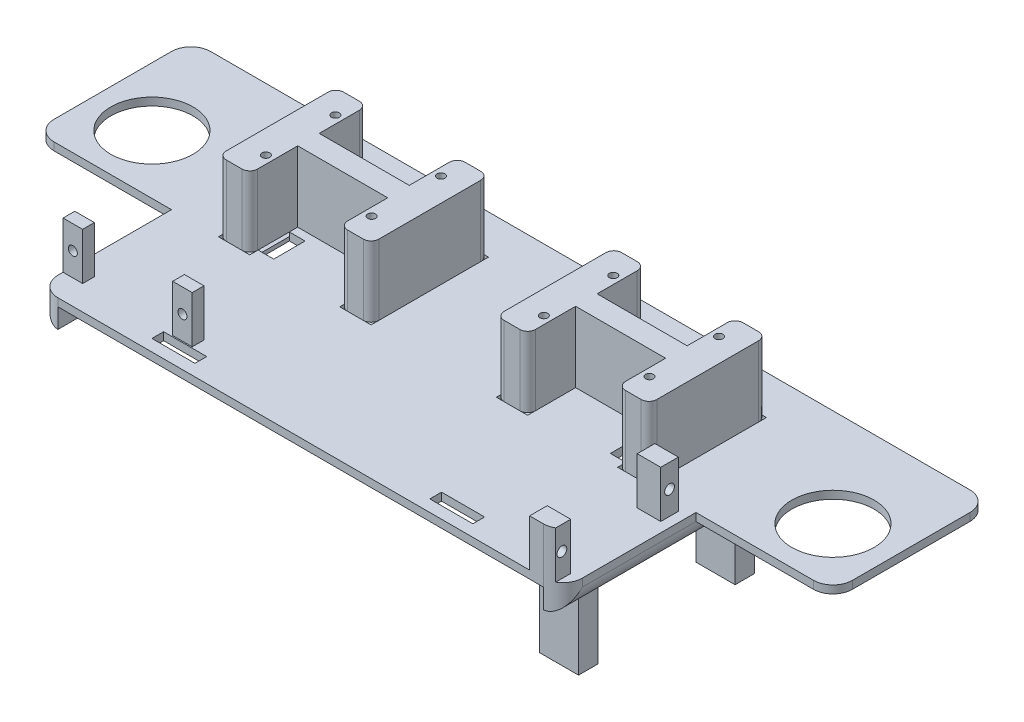
SolidWorks part; units mm, degrees
other "Controller Base"
other "HMount1"
other "HMount2"
ref_plane "Front Plane" through (0, 0, 0) normal (0, 0, 1) x (1, 0, 0)
ref_plane "Top Plane" through (0, 0, 0) normal (0, 1, 0) x (1, 0, 0)
ref_plane "Right Plane" through (0, 0, 0) normal (1, 0, 0) x (0, 0, -1)
sketch "Sketch1" plane through (0, 0, 0) normal (1, 0, 0) x (0, 0, -1)
  line L0 (0, 0) -> (0, 30)
  line L1 (0, 30) -> (45, 30)
  line L2 (45, 30) -> (45, 0)
  line L3 (45, 0) -> (40, 0)
  line L4 (40, 0) -> (40, 27)
  line L5 (40, 27) -> (5, 27)
  line L6 (5, 27) -> (5, 0)
  line L7 (5, 0) -> (0, 0)
  dimension "D1" = 5
  dimension "D2" = 5
  dimension "D3" = 3
  dimension "D4" = 35
  dimension "D5" = 30
extrude "C Bracket" add sketch "Sketch1" along normal blind 10
sketch "Sketch3" plane through (0, 30, 0) normal (0, 1, 0) x (1, 0, 0)
  line L0 (10, 45) -> (10, 0) construction
  line L1 (-113, -15) -> (21, -15)
  line L2 (-113, -15) -> (-113, 59)
  line L3 (-113, 59) -> (21, 59)
  line L4 (21, -15) -> (21, 59)
  line L5 (10, 0) -> (0, 0) construction
  line L6 (-148, 19) -> (-148, 59)
  line L7 (-113, 59) -> (-148, 59)
  line L8 (-46, 59) -> (-46, -15) construction
  line L9 (-113, 19) -> (-113, 59)
  line L10 (21, 19) -> (56, 19)
  line L11 (21, 19) -> (21, 59)
  line L12 (21, 59) -> (56, 59)
  line L13 (56, 19) -> (56, 59)
  line L14 (-113, 19) -> (-148, 19)
  line L15 (-113, -15) -> (-113, 59)
  circle A0 centre (41, 34) radius 10.5
  circle A1 centre (-133, 34) radius 10.5
  line M10 (0, 45) -> (0, 0)
  line M11 (0, 0) -> (10, 0)
  line M12 (10, 0) -> (10, 45)
  line M13 (10, 45) -> (0, 45)
  dimension "D9" = 21
  dimension "D1" = 74
  dimension "D2" = 134
  dimension "D3" = 11
  dimension "D4" = 15
  dimension "D5" = 25
  dimension "D6" = 20
  dimension "D7" = 35
  dimension "D8" = 40
extrude "Main Body" add sketch "Sketch3" along normal blind 2 separate body contours L8 L3 L2 L1 | L14 L2 L7 L6 A1 | L3 L8 L1 L4 M10 M13 M12 M11 | L10 L13 L12 L4 A0 | L2 L1 L4 L3 region at (-79.5, 30, -22) region at (-14.2469, 30, -21.9501) region at (-130.5, 30, -19.5315) region at (21.5315, 30, -39)
sketch "Sketch4" plane through (0, 30, 0) normal (0, -1, 0) x (1, 0, 0)
  line L0 (-148, -59) -> (56, -59) construction
  line L1 (-113, 15) -> (-108, 15)
  line L2 (-113, 15) -> (-113, -59)
  line L3 (-113, -59) -> (-108, -59)
  line L4 (-108, 15) -> (-108, -59)
  line L5 (-46, 15) -> (-46, -59) construction
  line L6 (-113, 15) -> (21, 15) construction
  line L7 (16, 15) -> (16, -59)
  line L8 (21, -59) -> (16, -59)
  line L9 (21, 15) -> (21, -59)
  line L10 (21, 15) -> (16, 15)
  dimension "D1" = 5
extrude "Boss-Extrude4" add sketch "Sketch4" along normal blind 5
sketch "Sketch6" plane through (0, 30, 0) normal (0, -1, 0) x (1, 0, 0)
  line L0 (0, -45) -> (0, 0) construction
  line L1 (10, -45) -> (0, -45) construction
  line L2 (10, -45) -> (10, 0) construction
  line L3 (10, 0) -> (0, 0) construction
  line L4 (0, -45) -> (0, 0)
  line L5 (10, -45) -> (0, -45)
  line L6 (10, -45) -> (10, 0)
  line L7 (10, 0) -> (0, 0)
extrude "C Bracket Insert" cut sketch "Sketch6" against normal blind 1
sketch "Sketch5" plane through (0, 32, 0) normal (0, 1, 0) x (1, 0, 0)
  line L0 (41, 34) -> (-133, 34) construction
  line L1 (-46, 59) -> (-46, -15) construction
  line L2 (-148, 59) -> (56, 59) construction
  line L3 (-113, -15) -> (21, -15) construction
  line L4 (-10.5, 36.75) -> (-10.5, 31.25) construction
  line L5 (-22, 31.25) -> (1, 31.25)
  line L7 (-22, 36.75) -> (1, 36.75)
  line L9 (1, 19) -> (1, 31.25)
  line L10 (-22, 19) -> (-30, 19)
  line L11 (-22, 19) -> (-22, 31.25)
  line L12 (-22, 49) -> (-30, 49)
  line L13 (-30, 19) -> (-30, 49)
  line L14 (9, 19) -> (9, 49)
  line L15 (1, 49) -> (9, 49)
  line L16 (1, 19) -> (9, 19)
  line L17 (-22, 36.75) -> (-22, 49)
  line L18 (1, 36.75) -> (1, 49)
  line L19 (-17.74, 36.75) -> (-17.74, 34) construction
  line L20 (-16.5781, 34) -> (-16.5781, 31.25) construction
  line L21 (-75.4219, 34) -> (-75.4219, 31.25) construction
  line L22 (-74.26, 36.75) -> (-74.26, 34) construction
  line L23 (-81.5, 36.75) -> (-81.5, 31.25) construction
  line L24 (-93, 36.75) -> (-93, 49)
  line L25 (-70, 36.75) -> (-70, 49)
  line L26 (-93, 19) -> (-101, 19)
  line L27 (-93, 49) -> (-101, 49)
  line L28 (-101, 19) -> (-101, 49)
  line L29 (-62, 19) -> (-62, 49)
  line L30 (-70, 49) -> (-62, 49)
  line L31 (-70, 19) -> (-70, 31.25)
  line L32 (-70, 19) -> (-62, 19)
  line L33 (-93, 19) -> (-93, 31.25)
  line L34 (-70, 36.75) -> (-93, 36.75)
  line L35 (-70, 31.25) -> (-93, 31.25)
  circle A0 centre (41, 34) radius 10.5 construction
  circle A1 centre (41, 34) radius 10.5
  point P22 (-30, 34)
  dimension "D1" = 5.5
  dimension "D2" = 23
  dimension "D3" = 30
  dimension "D4" = 8
  dimension "D5" = 32
extrude "Motor Holders" add sketch "Sketch5" along normal blind 18 separate body contours L24 L27 L28 L26 L33 L35 L31 L32 L29 L30 L25 L34 | L5 L9 L16 L14 L15 L18 L7 L17 L12 L13 L10 L11
sketch "Sketch11" plane through (0, 32, 0) normal (0, 1, 0) x (1, 0, 0)
  line L0 (-22, 36.75) -> (-22, 49) construction
  line L1 (-22, 49) -> (-30, 49) construction
  line L2 (-30, 19) -> (-30, 49) construction
  line L3 (-22, 19) -> (-30, 19) construction
  line L4 (-22, 19) -> (-22, 31.25) construction
  line L5 (-22, 31.25) -> (1, 31.25) construction
  line L6 (-22, 36.75) -> (1, 36.75) construction
  line L7 (1, 36.75) -> (1, 49) construction
  line L8 (1, 19) -> (1, 31.25) construction
  line L9 (1, 19) -> (9, 19) construction
  line L10 (9, 19) -> (9, 49) construction
  line L11 (1, 49) -> (9, 49) construction
  line L12 (-70, 19) -> (-70, 31.25) construction
  line L13 (-70, 19) -> (-62, 19) construction
  line L14 (-62, 19) -> (-62, 49) construction
  line L15 (-70, 49) -> (-62, 49) construction
  line L16 (-70, 36.75) -> (-70, 49) construction
  line L17 (-70, 36.75) -> (-93, 36.75) construction
  line L18 (-70, 31.25) -> (-93, 31.25) construction
  line L19 (-93, 19) -> (-101, 19) construction
  line L20 (-93, 19) -> (-93, 31.25) construction
  line L21 (-93, 36.75) -> (-93, 49) construction
  line L22 (-93, 49) -> (-101, 49) construction
  line L23 (-101, 19) -> (-101, 49) construction
  line L24 (-22, 36.75) -> (-22, 49)
  line L25 (-22, 49) -> (-30, 49)
  line L26 (-30, 19) -> (-30, 49)
  line L27 (-22, 19) -> (-30, 19)
  line L28 (-22, 19) -> (-22, 31.25)
  line L29 (-22, 31.25) -> (1, 31.25)
  line L30 (-22, 36.75) -> (1, 36.75)
  line L31 (1, 36.75) -> (1, 49)
  line L32 (1, 19) -> (1, 31.25)
  line L33 (1, 19) -> (9, 19)
  line L34 (9, 19) -> (9, 49)
  line L35 (1, 49) -> (9, 49)
  line L36 (-70, 19) -> (-70, 31.25)
  line L37 (-70, 19) -> (-62, 19)
  line L38 (-62, 19) -> (-62, 49)
  line L39 (-70, 49) -> (-62, 49)
  line L40 (-70, 36.75) -> (-70, 49)
  line L41 (-70, 36.75) -> (-93, 36.75)
  line L42 (-70, 31.25) -> (-93, 31.25)
  line L43 (-93, 19) -> (-101, 19)
  line L44 (-93, 19) -> (-93, 31.25)
  line L45 (-93, 36.75) -> (-93, 49)
  line L46 (-93, 49) -> (-101, 49)
  line L47 (-101, 19) -> (-101, 49)
extrude "Motor Holder Insert" cut sketch "Sketch11" against normal blind 1
sketch "Sketch12" plane through (0, 50, 0) normal (0, 1, 0) x (1, 0, 0)
  line L0 (1, 42.875) -> (9, 42.875) construction
  line L1 (1, 49) -> (1, 36.75) construction
  line L2 (9, 19) -> (9, 49) construction
  line L3 (-3, 21.125) -> (1, 29.125) construction
  line L8 (-10.5, 36.75) -> (-10.5, 59) construction
  line L9 (-22, 36.75) -> (1, 36.75) construction
  line L10 (-148, 59) -> (56, 59) construction
  line L11 (1, 36.75) -> (1, 49) construction
  line L12 (-3, 38.875) -> (1, 38.875)
  line L13 (-3, 38.875) -> (-3, 46.875)
  line L14 (-3, 46.875) -> (1, 46.875)
  line L15 (1, 38.875) -> (1, 46.875)
  line L16 (-3, 38.875) -> (1, 46.875) construction
  line L17 (-3, 46.875) -> (1, 38.875) construction
  line L18 (-30, 34) -> (9, 34) construction
  line L19 (-16, 53) -> (-5, 53)
  line L20 (-16, 53) -> (-16, 56)
  line L21 (-16, 56) -> (-5, 56)
  line L22 (-5, 53) -> (-5, 56)
  line L23 (-16, 53) -> (-5, 56) construction
  line L24 (-16, 56) -> (-5, 53) construction
  line L25 (-30, 19) -> (-30, 49) construction
  line L26 (9, 19) -> (9, 49) construction
  line L27 (-46, 59) -> (-46, -15) construction
  line L28 (-113, -15) -> (21, -15) construction
  line L29 (21, -15) -> (21, 59) construction
  line L30 (21, 22) -> (-114.2213, 22) construction
  line L31 (-3, 29.125) -> (1, 21.125) construction
  line L32 (1, 25.125) -> (9, 25.125) construction
  line L33 (1, 29.125) -> (1, 21.125)
  line L34 (-3, 21.125) -> (1, 21.125)
  line L35 (-3, 29.125) -> (-3, 21.125)
  line L36 (-3, 29.125) -> (1, 29.125)
  line L37 (-16, -12) -> (-5, -9) construction
  line L38 (-16, -9) -> (-5, -12) construction
  line L39 (-5, -9) -> (-5, -12)
  line L40 (-16, -12) -> (-5, -12)
  line L41 (-16, -9) -> (-16, -12)
  line L42 (-16, -9) -> (-5, -9)
  line L43 (-76, -9) -> (-87, -12) construction
  line L44 (-76, -12) -> (-87, -9) construction
  line L45 (-93, 25.125) -> (-101, 25.125) construction
  line L46 (-89, 29.125) -> (-93, 21.125) construction
  line L47 (-113, -15) -> (-113, 59) construction
  line L48 (-76, 56) -> (-87, 53) construction
  line L49 (-76, 53) -> (-87, 56) construction
  line L50 (-62, 34) -> (-101, 34) construction
  line L51 (-89, 46.875) -> (-93, 38.875) construction
  line L52 (-89, 38.875) -> (-93, 46.875) construction
  line L53 (-81.5, 36.75) -> (-81.5, 59) construction
  line L54 (-89, 21.125) -> (-93, 29.125) construction
  line L55 (-93, 42.875) -> (-101, 42.875) construction
  line L56 (-76, -9) -> (-87, -9)
  line L57 (-76, -9) -> (-76, -12)
  line L58 (-76, -12) -> (-87, -12)
  line L59 (-87, -9) -> (-87, -12)
  line L60 (-89, 29.125) -> (-93, 29.125)
  line L61 (-89, 29.125) -> (-89, 21.125)
  line L62 (-89, 21.125) -> (-93, 21.125)
  line L63 (-93, 29.125) -> (-93, 21.125)
  line L64 (-87, 53) -> (-87, 56)
  line L65 (-76, 56) -> (-87, 56)
  line L66 (-76, 53) -> (-76, 56)
  line L67 (-76, 53) -> (-87, 53)
  line L68 (-93, 38.875) -> (-93, 46.875)
  line L69 (-89, 46.875) -> (-93, 46.875)
  line L70 (-89, 38.875) -> (-89, 46.875)
  line L71 (-89, 38.875) -> (-93, 38.875)
  circle A0 centre (3, 42.875) radius 1
  circle A1 centre (3, 25.125) radius 1
  circle A2 centre (-24, 25.125) radius 1
  circle A3 centre (-24, 42.875) radius 1
  circle A4 centre (-68, 42.875) radius 1
  circle A5 centre (-68, 25.125) radius 1
  circle A6 centre (-95, 25.125) radius 1
  circle A7 centre (-95, 42.875) radius 1
  point P6 (-1, 42.875)
  point P20 (-10.5, 54.5)
  point P50 (-1, 25.125)
  point P59 (-10.5, -10.5)
  point P94 (-81.5, -10.5)
  point P95 (-91, 25.125)
  point P96 (-81.5, 54.5)
  point P97 (-91, 42.875)
  dimension "D6" = 2
  dimension "D1" = 3
  dimension "D2" = 3
  dimension "D3" = 11
  dimension "D4" = 4
  dimension "D5" = 8
  dimension "D7" = 2
extrude "Strap and Screw Holes" cut sketch "Sketch12" against normal up to surface (20 mm away) up to face at (5, 30, -22.5)
sketch "Sketch13" plane through (0, 32, 0) normal (0, 1, 0) x (1, 0, 0)
  line L0 (-113, -15) -> (21, -15) construction
  line L1 (18.5, -15) -> (12.5, -15)
  line L2 (18.5, -15) -> (18.5, -10.5)
  line L3 (18.5, -10.5) -> (12.5, -10.5)
  line L4 (12.5, -15) -> (12.5, -10.5)
  line L5 (21, -15) -> (21, 19) construction
  line L6 (18.5, 12.5) -> (12.5, 12.5)
  line L7 (18.5, 12.5) -> (18.5, 17)
  line L8 (18.5, 17) -> (12.5, 17)
  line L9 (12.5, 12.5) -> (12.5, 17)
  dimension "D1" = 2.5
  dimension "D2" = 6
  dimension "D3" = 4.5
  dimension "D4" = 6
  dimension "D5" = 2.5
  dimension "D6" = 23
  dimension "D7" = 4.5
extrude "Boss-Extrude8" add sketch "Sketch13" along normal blind 12
sketch "Sketch14" plane through (18.5, 0, 0) normal (1, 0, 0) x (0, 0, -1)
  line L0 (-12.75, 44) -> (-12.75, 32) construction
  line L1 (-15, 44) -> (-10.5, 44) construction
  line L2 (-15, 32) -> (-10.5, 32) construction
  line L3 (14.75, 44) -> (14.75, 32) construction
  line L4 (12.5, 44) -> (17, 44) construction
  line L5 (12.5, 32) -> (17, 32) construction
  circle A0 centre (-12.75, 38) radius 1.25
  circle A1 centre (14.75, 38) radius 1.25
  dimension "D3" = 2.5
  dimension "D1" = 6
  dimension "D2" = 6
extrude "Cut-Extrude6" cut sketch "Sketch14" against normal up to surface (6 mm away) up to face at (12.5, 38, 12.75)
sketch "Sketch15" plane through (0, 32, 0) normal (0, 1, 0) x (1, 0, 0)
  line L0 (-113, -15) -> (12.5, -15) construction
  line L1 (-108, -8.7) -> (-113, -8.7)
  line L2 (-108, -8.7) -> (-108, -5.7)
  line L3 (-108, -5.7) -> (-113, -5.7)
  line L4 (-113, -8.7) -> (-113, -5.7)
  line L5 (-108, -8.7) -> (-113, -5.7) construction
  line L6 (-108, -5.7) -> (-113, -8.7) construction
  line L7 (-80, -8.7) -> (-85, -8.7)
  line L8 (-80, -8.7) -> (-80, -5.7)
  line L9 (-80, -5.7) -> (-85, -5.7)
  line L10 (-85, -8.7) -> (-85, -5.7)
  line L11 (-80, -8.7) -> (-85, -5.7) construction
  line L12 (-80, -5.7) -> (-85, -8.7) construction
  line L14 (-113, -15) -> (-113, 19) construction
  point P0 (-110.5, -7.2)
  point P5 (-82.5, -7.2)
  dimension "D1" = 23
  dimension "D2" = 3
  dimension "D3" = 5
  dimension "D4" = 9.3
extrude "Boss-Extrude9" add sketch "Sketch15" along normal blind 12
sketch "Sketch16" plane through (0, 0, 8.7) normal (0, 0, 1) x (1, 0, 0)
  line L0 (-110.5, 44) -> (-110.5, 32) construction
  line L1 (-113, 44) -> (-108, 44) construction
  line L2 (-113, 32) -> (-108, 32) construction
  line L3 (-82.5, 44) -> (-82.5, 32) construction
  line L4 (-85, 44) -> (-80, 44) construction
  line L5 (-113, 32) -> (12.5, 32) construction
  line L6 (-85, 32) -> (-80, 32) construction
  circle A0 centre (-110.5, 38) radius 1.15
  circle A1 centre (-82.5, 38) radius 1.15
  dimension "D3" = 2.3
  dimension "D1" = 6
  dimension "D2" = 6
extrude "Cut-Extrude7" cut sketch "Sketch16" against normal up to surface (3 mm away) up to face at (-110.5, 38, 5.7)
fillet "Fillet1" radius 5 8 edges at (-113, 25, -22) (21, 25, -22) (21, 28.5, 15) (-113, 28.5, 15) (56, 31, -19) (56, 31, -59) (-148, 31, -19) (-148, 31, -59)
fillet "Fillet2" radius 2 8 edges at (-70, 41, -19) (-62, 41, -19) (-62, 41, -49) (-70, 41, -49) (-93, 41, -49) (-101, 41, -49) (-93, 41, -19) (-101, 41, -19)
fillet "Fillet3" radius 2 8 edges at (1, 41, -19) (9, 41, -19) (1, 41, -49) (9, 41, -49) (-30, 41, -49) (-22, 41, -49) (-22, 41, -19) (-30, 41, -19)
